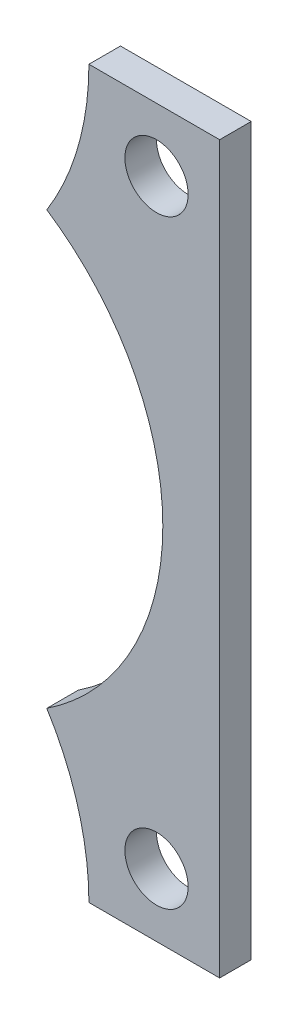
SolidWorks part; units mm, degrees
ref_plane "Front Plane" through (0, 0, 0) normal (0, 0, 1) x (1, 0, 0)
ref_plane "Top Plane" through (0, 0, 0) normal (0, 1, 0) x (1, 0, 0)
ref_plane "Right Plane" through (0, 0, 0) normal (1, 0, 0) x (0, 0, -1)
sketch "Sketch1" plane through (0, 0, 0) normal (0, 0, 1) x (1, 0, 0)
  line L0 (-7.2461, 73.025) -> (-7.2461, -73.025) construction
  line L1 (-19.05, -73.025) -> (19.05, -73.025)
  line L2 (-19.05, -73.025) -> (-19.05, 73.025)
  line L3 (-19.05, 73.025) -> (19.05, 73.025)
  line L4 (19.05, -73.025) -> (19.05, 73.025)
  line L5 (-19.05, -73.025) -> (19.05, 73.025) construction
  line L6 (-19.05, 73.025) -> (19.05, -73.025) construction
  line L7 (-44.45, 20.32) -> (-44.45, -20.32) construction
  line L8 (-44.45, 0) -> (0, 0) construction
  circle A0 centre (-44.45, 0) radius 52.07
  circle A1 centre (6.35, 60.325) radius 6.3627
  circle A2 centre (6.35, -60.325) radius 6.3627
  arc A3 (-7.2461, 73.025) -> (-19.05, 45.4546) centre (-45.3461, 73.025) cw
  circle A4 centre (-44.45, 0) radius 20.32
  arc A5 (-7.2461, 73.025) -> (-44.45, 20.32) centre (-63.1804, 73.025) cw
  arc A6 (-7.2461, -73.025) -> (-44.45, -20.32) centre (-63.1804, -73.025) ccw
  point P0 (0, 0)
  dimension "D2" = 104.14
  dimension "D3" = 12.7254
  dimension "D9" = 38.1
  dimension "D10" = 40.64
  dimension "D1" = 146.05
  dimension "D4" = 12.7
  dimension "D5" = 12.7
  dimension "D6" = 50.8
  dimension "D7" = 38.1
  dimension "D8" = 12.7
extrude "Boss-Extrude1" add sketch "Sketch1" along normal mid plane 6.35 contours A6 L1 L4 L3 A5 A0 A2 A1 region at (-7.9628, -57.2179, 0)
